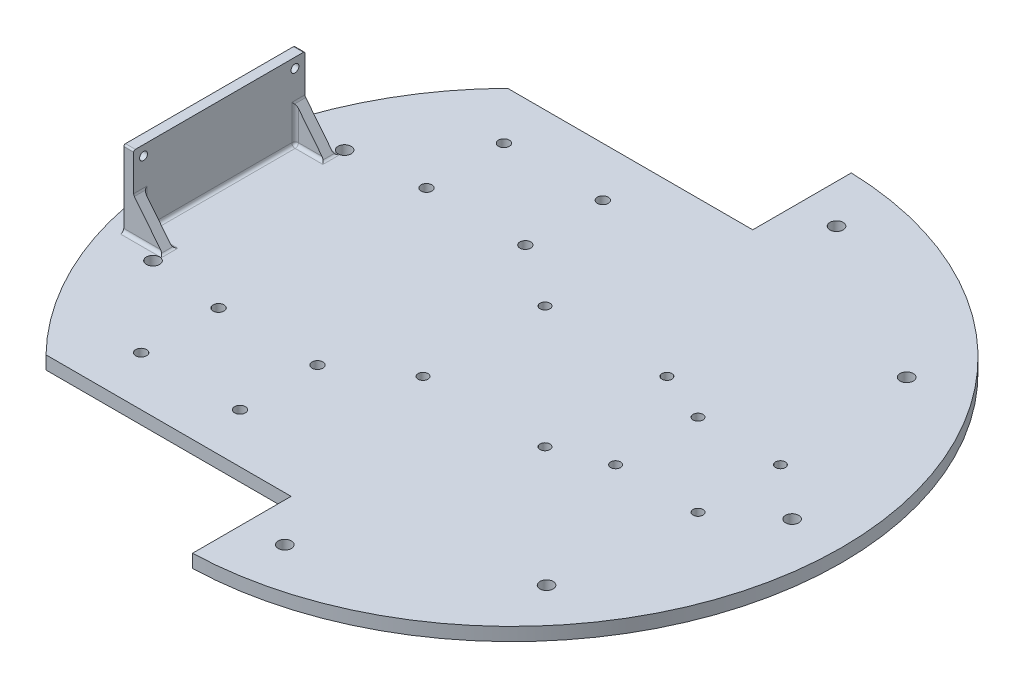
SolidWorks part; units mm, degrees
ref_plane "Спереди" through (0, 0, 0) normal (0, 0, 1) x (1, 0, 0)
ref_plane "Сверху" through (0, 0, 0) normal (0, 1, 0) x (1, 0, 0)
ref_plane "Справа" through (0, 0, 0) normal (1, 0, 0) x (0, 0, -1)
other "Configuration Table"
sketch "Эскиз1" plane through (0, 0, 0) normal (0, 1, 0) x (1, 0, 0)
  circle A0 centre (0, 0) radius 100
extrude "Бобышка-Вытянуть1" add sketch "Эскиз1" along normal blind 4
sketch "Эскиз3" plane through (0, 4, 0) normal (0, 1, 0) x (1, 0, 0)
  line L0 (-100, 0) -> (100, 0) construction
  line L2 (-42, -87.543) -> (-42, 90.7524) construction
  line L3 (-87, 70.043) -> (3, 105.043) construction
  line L4 (-87, -105.043) -> (3, -105.043)
  line L5 (-87, -105.043) -> (-87, -70.043)
  line L6 (-87, -70.043) -> (3, -70.043)
  line L7 (3, -105.043) -> (3, -70.043)
  line L8 (-87, -105.043) -> (3, -70.043) construction
  line L9 (-87, -70.043) -> (3, -105.043) construction
  line L10 (-87, 105.043) -> (3, 70.043) construction
  line L11 (3, 105.043) -> (3, 70.043)
  line L12 (-87, 70.043) -> (3, 70.043)
  line L13 (-87, 105.043) -> (-87, 70.043)
  line L14 (-87, 105.043) -> (3, 105.043)
  circle A0 centre (0, 0) radius 100 construction
  point P10 (-42, 1.6047)
extrude "Вырез-Вытянуть1" cut sketch "Эскиз3" against normal blind 10
sketch "Эскиз4" plane through (0, 4, 0) normal (0, 1, 0) x (1, 0, 0)
  line L0 (-100, 0) -> (100, 0) construction
  line L2 (-42.5, -75.043) -> (-42.5, 70.043) construction
  line L3 (-71.3721, 70.043) -> (3, 70.043) construction
  arc A0 (-71.3721, 70.043) -> (-71.3721, -70.043) centre (0, 0) ccw construction
  arc A1 (3, -99.955) -> (3, 99.955) centre (0, 0) ccw construction
  circle A2 centre (-57.5, -55.043) radius 1.65
  circle A3 centre (-27.5, -55.043) radius 1.65
  circle A4 centre (-57.5, -31.543) radius 1.65
  circle A5 centre (-27.5, -31.543) radius 1.65
  circle A6 centre (-27.5, 31.543) radius 1.65
  circle A7 centre (-57.5, 31.543) radius 1.65
  circle A8 centre (-27.5, 55.043) radius 1.65
  circle A9 centre (-57.5, 55.043) radius 1.65
  point P15 (-42.5, -2.5)
  point P19 (-42.5, -55.043)
  point P30 (-42.5, 55.043)
extrude "Вырез-Вытянуть2" cut sketch "Эскиз4" against normal blind 10
sketch "Эскиз6" plane through (0, 4, 0) normal (0, 1, 0) x (1, 0, 0)
  circle A2 centre (85, 0) radius 2
  circle A3 centre (65.1138, -54.6369) radius 2
  circle A4 centre (14.7601, -83.7087) radius 2
  circle A6 centre (-79.8739, -29.0717) radius 2
  circle A7 centre (-79.8739, 29.0717) radius 2
  circle A9 centre (14.7601, 83.7087) radius 2
  circle A10 centre (65.1138, 54.6369) radius 2
  circle A11 centre (-42.5, 73.6122) radius 2 [skipped]
  circle A12 centre (-42.5, -73.6122) radius 2 [skipped]
  point P23 (0, 0)
  dimension "D1" = 9
extrude "Вырез-Вытянуть3" cut sketch "Эскиз6" against normal blind 50
sketch "Эскиз7" plane through (0, 4, 0) normal (0, 1, 0) x (1, 0, 0)
  circle A0 centre (-8.5, 18.5) radius 1.5
  circle A1 centre (28.5, 18.5) radius 1.5
  circle A2 centre (28.5, -18.5) radius 1.5
  circle A3 centre (-8.5, -18.5) radius 1.5
extrude "Вырез-Вытянуть4" cut sketch "Эскиз7" against normal blind 10
sketch "Эскиз8" plane through (0, 4, 0) normal (0, 1, 0) x (1, 0, 0)
  line L0 (100, 0) -> (-100, 0) construction
  line L2 (-91.8177, -26) -> (-88.8177, -26)
  line L3 (-91.8177, -26) -> (-91.8177, 26)
  line L4 (-91.8177, 26) -> (-88.8177, 26)
  line L5 (-88.8177, -26) -> (-88.8177, 26)
  line L6 (-91.8177, -26) -> (-88.8177, 26) construction
  line L7 (-91.8177, 26) -> (-88.8177, -26) construction
  arc A0 (-71.3721, 70.043) -> (-71.3721, -70.043) centre (0, 0) ccw construction
  point P0 (-90.3177, 0)
  point P7 (0, 0)
extrude "Бобышка-Вытянуть2" add sketch "Эскиз8" along normal blind 23
fillet "Скругление1" radius 0.5 2 edges at (-90.3177, 27, 26) (-90.3177, 27, -26)
sketch "Эскиз10" plane through (0, 0, 26) normal (0, 0, 1) x (1, 0, 0)
  line L0 (-88.8177, 15.25) -> (-79.8739, 4)
  line L1 (-88.8177, 26.5) -> (-88.8177, 4) construction
  line L2 (-77.8739, 4) -> (-81.8739, 4) construction
rib "Ребро1" sketch "Эскиз10" sketch "Эскиз10" thickness 3 extrusion direction parallel to sketch draft on no parameters "D1"=3
sketch "Эскиз12" plane through (0, 0, -26) normal (0, 0, -1) x (-1, 0, 0)
  line L0 (88.8177, 15.25) -> (79.8739, 4)
  line L1 (88.8177, 26.5) -> (88.8177, 4) construction
rib "Ребро15" sketch "Эскиз12" sketch "Эскиз12" thickness 3 extrusion direction parallel to sketch draft on no parameters "D1"=3
fillet "Скругление2" radius 1 1 edges at (-79.8739, 4, 24.5)
fillet "Скругление3" radius 1 1 edges at (-88.8177, 15.25, 24.5)
fillet "Скругление4" radius 1 1 edges at (-88.8177, 15.25, -24.5)
fillet "Скругление5" radius 1 1 edges at (-79.8739, 4, -24.5)
fillet "Скругление6" radius 1 1 edges at (-88.8177, 4, 0)
fillet "Скругление7" radius 1 8 edges at (-88.8177, 10.2995, -23) (-88.5249, 4.2929, -23) (-88.8177, 10.2995, 23) (-88.5249, 4.2929, 23) (-85.6046, 4, -26) (-83.6046, 4, -23) (-83.6046, 4, 23) (-85.6046, 4, 26)
sketch "Эскиз13" plane through (-91.8177, 0, 0) normal (-1, 0, 0) x (0, 0, 1)
  circle A1 centre (-22.9404, 24.0649) radius 1.2
  circle A2 centre (23, 24) radius 1.2
  circle A3 centre (-23, 7) radius 1.2
  circle A4 centre (23, 7) radius 1.2
  point P6 (0, 15.5)
extrude "Вырез-Вытянуть6" cut sketch "Эскиз13" against normal blind 2
sketch "Эскиз14" plane through (-89.8177, 0, 0) normal (-1, 0, 0) x (0, 0, 1)
  circle A0 centre (-22.9404, 24.0649) radius 1.2
  circle A1 centre (23, 24) radius 1.2
extrude "Вырез-Вытянуть7" cut sketch "Эскиз14" against normal blind 2
sketch "Эскиз15" plane through (0, 4, 0) normal (0, 1, 0) x (1, 0, 0)
  line L0 (0, 0) -> (100, 0) construction
  arc A0 (3, -99.955) -> (3, 99.955) centre (0, 0) ccw construction
  circle A1 centre (43.9373, 12.5) radius 1.5
  circle A2 centre (68.9373, 12.5) radius 1.5
  circle A3 centre (43.9373, -12.5) radius 1.5
  circle A4 centre (68.9373, -12.5) radius 1.5
extrude "Вырез-Вытянуть8" cut sketch "Эскиз15" against normal blind 10
